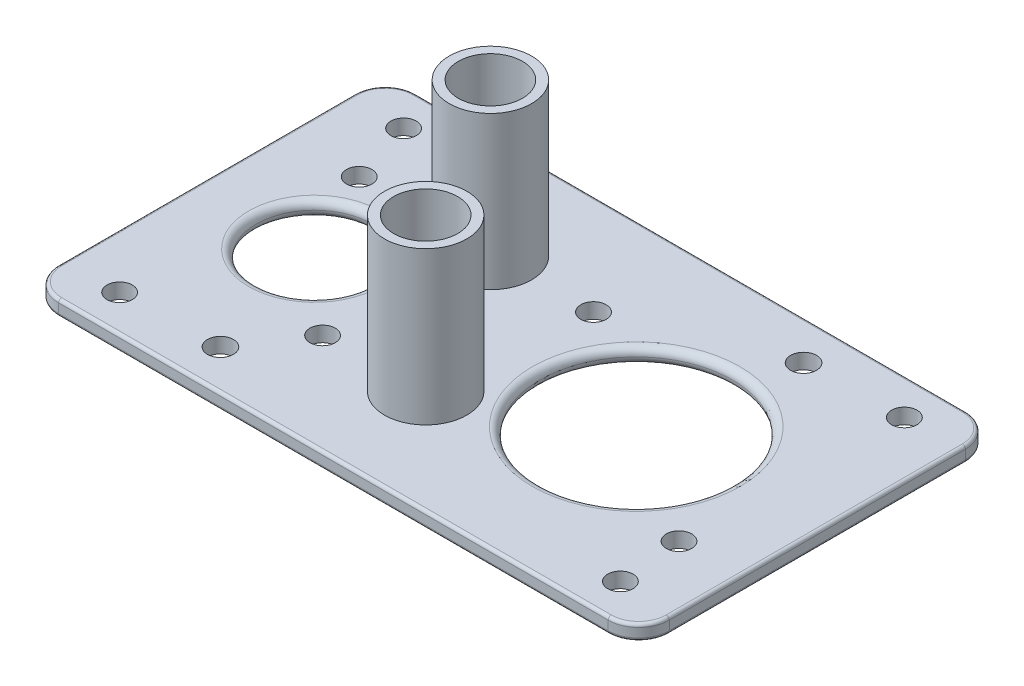
SolidWorks part; units mm, degrees
ref_plane "Front Plane" through (0, 0, 0) normal (0, 0, 1) x (1, 0, 0)
ref_plane "Top Plane" through (0, 0, 0) normal (0, 1, 0) x (1, 0, 0)
ref_plane "Right Plane" through (0, 0, 0) normal (1, 0, 0) x (0, 0, -1)
sketch "Sketch1" plane through (0, 0, 0) normal (0, 1, 0) x (1, 0, 0)
  line L1 (0, 0) -> (200, 0)
  line L2 (0, 0) -> (0, 117)
  line L3 (0, 117) -> (200, 117)
  line L4 (200, 0) -> (200, 117)
  line L5 (6.4676, 96) -> (81.4676, 96)
  line L6 (6.4676, 96) -> (6.4676, 21)
  line L7 (6.4676, 21) -> (81.4676, 21)
  line L8 (81.4676, 96) -> (81.4676, 21)
  line L9 (83.1891, 96) -> (198.1891, 96)
  line L10 (83.1891, 96) -> (83.1891, 21)
  line L11 (83.1891, 21) -> (198.1891, 21)
  line L12 (198.1891, 96) -> (198.1891, 21)
  circle A0 centre (18, 105) radius 4.15
  circle A1 centre (18, 12) radius 4.15
  circle A2 centre (182, 105) radius 4.15
  circle A3 centre (182, 12) radius 4.15
  circle A4 centre (24.4676, 84) radius 4.15
  circle A6 centre (63.4676, 33) radius 4.15
  circle A8 centre (101.1891, 84) radius 4.15
  circle A10 centre (180.1891, 33) radius 4.15
  circle A19 centre (50, 13.015) radius 4.25
  circle A20 centre (150, 103.985) radius 4.25
  circle A21 centre (68.4476, 82.98) radius 10
  circle A22 centre (96.2091, 34.02) radius 10
  dimension "D1" = 8.3
  dimension "D38" = 8.3
  dimension "D43" = 8.5
  dimension "D44" = 8.5
  dimension "D46" = 13.02
  dimension "D48" = 8.3
  dimension "D45" = 8.3
  dimension "D15" = 8.3
  dimension "D20" = 20
  dimension "D49" = 20
  dimension "D3" = 18
  dimension "D4" = 12
  dimension "D5" = 12
  dimension "D6" = 18
  dimension "D7" = 18
  dimension "D8" = 12
  dimension "D9" = 12
  dimension "D10" = 18
  dimension "D11" = 34.02
  dimension "D12" = 34.02
  dimension "D13" = 18
  dimension "D14" = 12
  dimension "D16" = 13.02
  dimension "D19" = 13.02
  dimension "D21" = 18
  dimension "D22" = 12
  dimension "D23" = 18
  dimension "D24" = 12
  dimension "D25" = 18
  dimension "D26" = 12
  dimension "D27" = 18
  dimension "D28" = 75
  dimension "D29" = 75
  dimension "D30" = 115
  dimension "D31" = 75
  dimension "D32" = 21
  dimension "D33" = 21
  dimension "D34" = 6.4676
  dimension "D35" = 1.8109
  dimension "D36" = 200
  dimension "D37" = 117
  dimension "D39" = 50
  dimension "D40" = 50
  dimension "D41" = 13.015
  dimension "D42" = 13.015
  dimension "D47" = 13.02
extrude "Boss-Extrude1" add sketch "Sketch1" along normal mid plane 5 contours L2 L1 L4 L3 | A0 | A4 | A6 | A8 | A2 | A20 | A10 | A3 | A1 | A19 | A21 | A22
sketch "Sketch3" plane through (0, 2.5, 0) normal (0, 1, 0) x (1, 0, 0)
  circle A0 centre (68.4476, 82.98) radius 13.5
  circle A1 centre (96.2091, 34.02) radius 13.5
  circle A2 centre (96.2091, 34.02) radius 10.5
  circle A3 centre (68.4476, 82.98) radius 10.5
  circle A4 centre (68.4476, 82.98) radius 10
  circle A5 centre (96.2091, 34.02) radius 10
  dimension "D1" = 20
  dimension "D2" = 21
  dimension "D3" = 3
  dimension "D4" = 20
  dimension "D5" = 21
  dimension "D6" = 3
extrude "Boss-Extrude3" add sketch "Sketch3" along normal blind 50 contours A0 | A3 | A1 | A2
sketch "Sketch4" plane through (0, 2.5, 0) normal (0, 1, 0) x (1, 0, 0)
  circle A0 centre (68.4476, 82.98) radius 8.5
  circle A1 centre (68.4476, 82.98) radius 10.5
  circle A2 centre (96.2091, 34.02) radius 8.5
  circle A3 centre (96.2091, 34.02) radius 10.5
  dimension "D1" = 17
  dimension "D2" = 21
  dimension "D3" = 17
  dimension "D4" = 21
extrude "Boss-Extrude4" add sketch "Sketch4" along normal blind 25
fillet "Fillet1" radius 10 4 edges at (0, 0, 0) (0, 0, -117) (200, 0, -117) (200, 0, 0)
fillet "Fillet2" radius 1 16 edges at (200, -2.5, -58.5) (197.0711, -2.5, -114.0711) (100, -2.5, -117) (2.9289, -2.5, -114.0711) (0, -2.5, -58.5) (2.9289, -2.5, -2.9289) (100, -2.5, 0) (2.9289, 2.5, -2.9289) (0, 2.5, -58.5) (2.9289, 2.5, -114.0711) (100, 2.5, -117) (197.0711, 2.5, -114.0711) (200, 2.5, -58.5) (197.0711, 2.5, -2.9289) (197.0711, -2.5, -2.9289) (100, 2.5, 0)
sketch "Sketch5" plane through (0, 2.5, 0) normal (0, 1, 0) x (1, 0, 0)
  arc A0 (129.2587, 87.853) -> (140.6891, 90) centre (140.6891, 58.5) ccw
  arc A1 (30.9073, 74.0505) -> (37.541, 75.2462) centre (37.541, 56.2462) ccw
  circle A7 centre (37.541, 56.2462) radius 19
  circle A9 centre (140.6891, 58.5) radius 31.5
  dimension "D3" = 38
  dimension "D4" = 63
  dimension "D5" = 56.2462
  dimension "D6" = 58.5
  dimension "D7" = 37.541
  dimension "D8" = 140.6891
  dimension "D9" = 17.8043
  dimension "D15" = 19
  dimension "D16" = 6.6337
  dimension "D18" = 31.5
  dimension "D20" = 29.353
extrude "Cut-Extrude3" cut sketch "Sketch5" against normal blind 123 contours A7 | A9
fillet "Fillet4" radius 2.5 4 edges at (37.541, -2.5, -37.2462) (37.541, 2.5, -37.2462) (140.6891, -2.5, -27) (140.6891, 2.5, -27)
